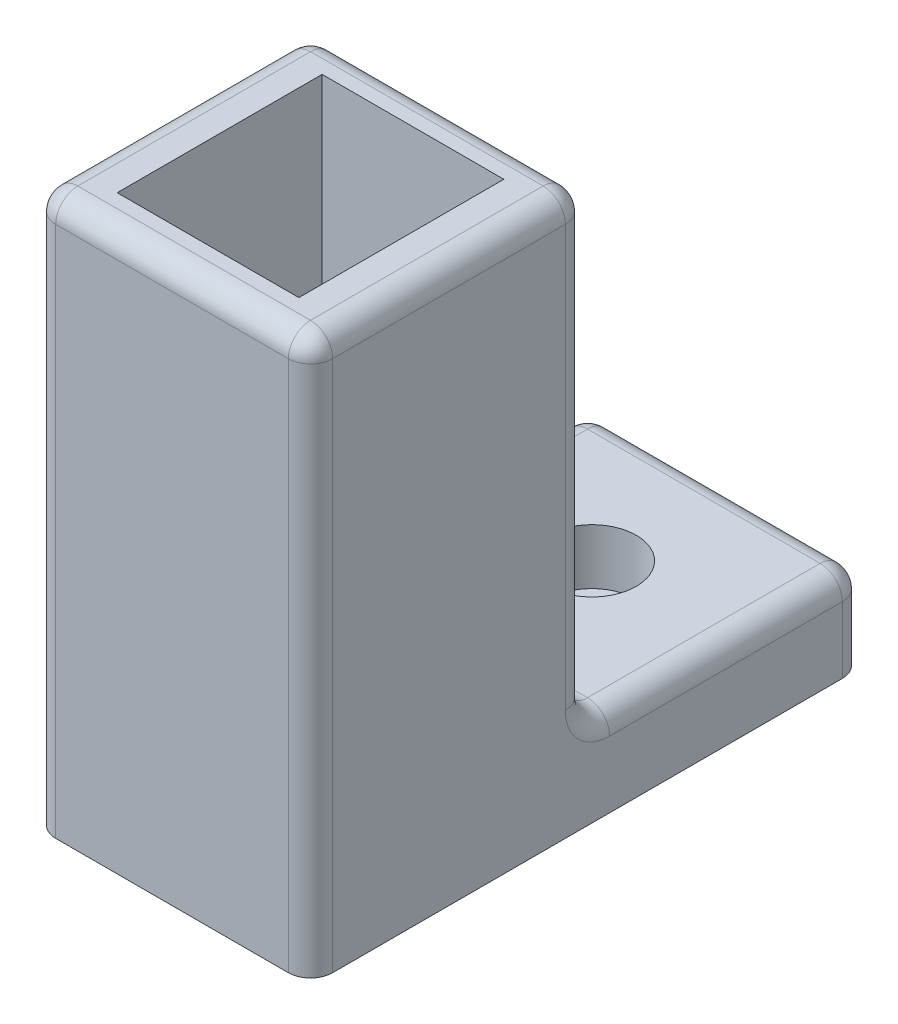
SolidWorks part; units mm, degrees
material "ABS"
ref_plane "Front Plane" through (0, 0, 0) normal (0, 0, 1) x (1, 0, 0)
ref_plane "Top Plane" through (0, 0, 0) normal (0, 1, 0) x (1, 0, 0)
ref_plane "Right Plane" through (0, 0, 0) normal (1, 0, 0) x (0, 0, -1)
sketch "Sketch1" plane through (0, 0, 0) normal (0, 1, 0) x (1, 0, 0)
  line L1 (-8.2, -9.25) -> (8.2, -9.25)
  line L2 (-8.2, -9.25) -> (-8.2, 9.25)
  line L3 (-8.2, 9.25) -> (8.2, 9.25)
  line L4 (8.2, -9.25) -> (8.2, 9.25)
  line L5 (-8.2, -9.25) -> (8.2, 9.25) construction
  line L6 (-8.2, 9.25) -> (8.2, -9.25) construction
  line L7 (-12.5, -12.5) -> (12.5, -12.5)
  line L8 (-12.5, -12.5) -> (-12.5, 12.5)
  line L9 (-12.5, 12.5) -> (12.5, 12.5)
  line L10 (12.5, -12.5) -> (12.5, 12.5)
  line L11 (-12.5, -12.5) -> (12.5, 12.5) construction
  line L12 (-12.5, 12.5) -> (12.5, -12.5) construction
  point P0 (0, 0)
  point P6 (0, 0)
  dimension "D1" = 16.4
  dimension "D2" = 18.5
  dimension "D3" = 25
  dimension "D4" = 25
extrude "Boss-Extrude1" add sketch "Sketch1" along normal blind 50
sketch "Sketch6" plane through (0, 0, 0) normal (0, 1, 0) x (1, 0, 0)
  line L9 (-12.5, -12.5) -> (12.5, -12.5)
  line L10 (-12.5, -12.5) -> (-12.5, 37.5)
  line L11 (-12.5, 37.5) -> (12.5, 37.5)
  line L12 (12.5, -12.5) -> (12.5, 37.5)
  dimension "D1" = 50
  dimension "D2" = 25
  dimension "D3" = 12.5
  dimension "D4" = 12.5
extrude "Boss-Extrude3" add sketch "Sketch6" along normal blind 8
fillet "Fillet2" radius 2 14 edges at (12.5, 4, -37.5) (-12.5, 4, -37.5) (-12.5, 8, -25) (0, 8, -37.5) (12.5, 8, -25) (0, 8, -12.5) (0, 50, -12.5) (12.5, 29, -12.5) (12.5, 50, 0) (12.5, 25, 12.5) (-12.5, 25, 12.5) (0, 50, 12.5) (-12.5, 29, -12.5) (-12.5, 50, 0)
sketch "Sketch7" plane through (0, 8, 0) normal (0, 1, 0) x (1, 0, 0)
  line L0 (0, 0) -> (0, 25.4) construction
  circle A0 centre (0, 0) radius 4
  circle A1 centre (0, 25.4) radius 4
extrude "Cut-Extrude1" cut sketch "Sketch7" against normal blind 5
sketch "Sketch8" plane through (0, 0, 0) normal (0, 1, 0) x (1, 0, 0)
  line L0 (0, 0) -> (0, 25.4) construction
  circle A0 centre (0, 0) radius 2.3813
  circle A1 centre (0, 25.4) radius 2.3813
extrude "Cut-Extrude4" cut sketch "Sketch8" against normal through all and the other way through all
